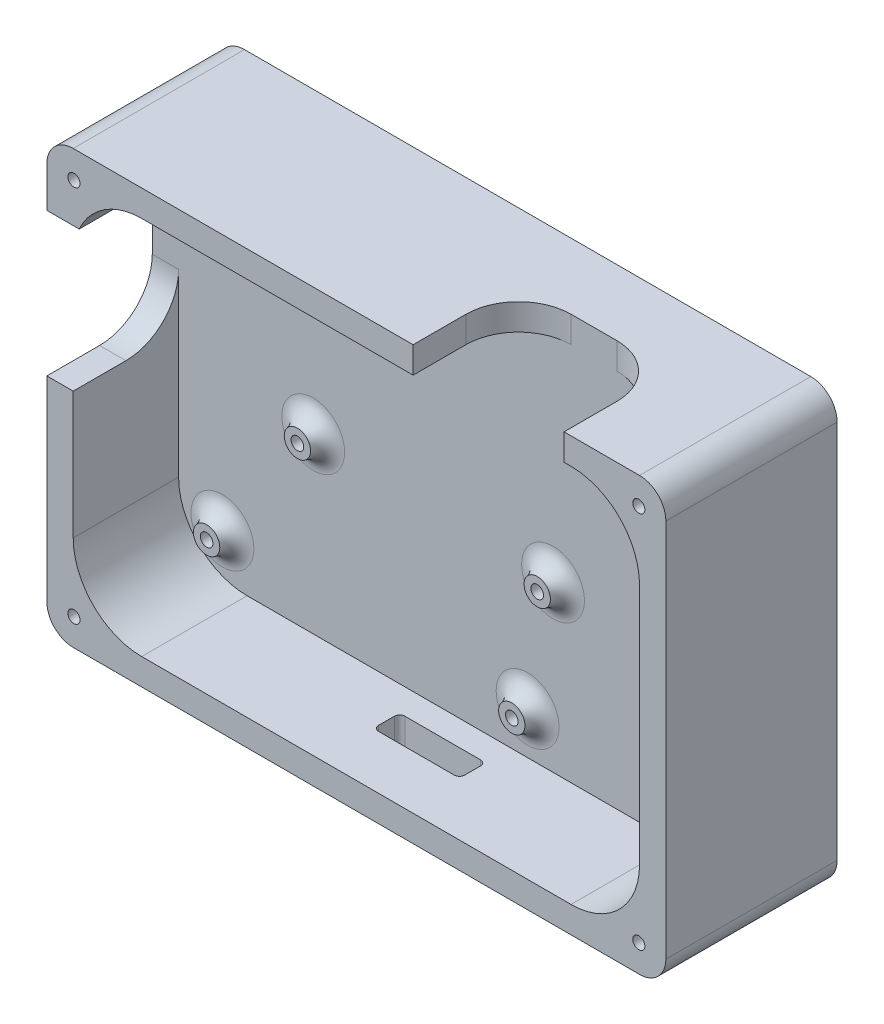
SolidWorks part; units mm, degrees
ref_plane "Front Plane" through (0, 0, 0) normal (0, 0, 1) x (1, 0, 0)
ref_plane "Top Plane" through (0, 0, 0) normal (0, 1, 0) x (1, 0, 0)
ref_plane "Right Plane" through (0, 0, 0) normal (1, 0, 0) x (0, 0, -1)
ref_plane "Plane1" through (0, 0, 1267.0007) normal (0, 0, -1) x (-1, 0, 0)
sketch "Sketch1" plane through (0, 0, 1267.0007) normal (0, 0, -1) x (-1, 0, 0)
  line L0 (-695.5296, 837.4474) -> (-695.5296, 897.8994) construction
  line L1 (-700.5296, 903.6614) -> (-593.0698, 903.6614)
  line L2 (-700.5296, 903.6614) -> (-700.5296, 831.66)
  line L3 (-700.5296, 831.66) -> (-593.0698, 831.66)
  line L4 (-593.0698, 903.6614) -> (-593.0698, 831.66)
  line L5 (-694.7676, 898.6614) -> (-598.8318, 898.6614) construction
  line L6 (-598.0698, 897.8994) -> (-598.0698, 837.4474) construction
  dimension "D1" = 5
  dimension "D2" = 5
  dimension "D3" = 5
  dimension "D4" = 5
extrude "Boss-Extrude1" add sketch "Sketch1" along normal blind 5
sketch "Sketch2" plane through (0, 0, 1267.0007) normal (0, 0, 1) x (1, 0, 0)
  circle A0 centre (692.0598, 895.8747) radius 2.5
  circle A1 centre (601.3798, 839.9968) radius 2.5
  circle A2 centre (692.0598, 862.8547) radius 2.5
  circle A3 centre (664.1198, 862.8547) radius 2.5
  circle A4 centre (602.0195, 895.2324) radius 2.5
  circle A5 centre (618.6145, 864.4774) radius 2.5
  circle A6 centre (659.2965, 839.6699) radius 2.5
  dimension "D1" = 5
extrude "Boss-Extrude2" add sketch "Sketch2" along normal up to surface (3 mm away)
fillet "Fillet1" radius 3.5 7 edges at (689.5598, 895.8747, 1267.0007) (689.5598, 862.8547, 1267.0007) (661.6198, 862.8547, 1267.0007) (616.1145, 864.4774, 1267.0007) (656.7965, 839.6699, 1267.0007) (599.5195, 895.2324, 1267.0007) (598.8798, 839.9968, 1267.0007)
sketch "Sketch3" plane through (0, 0, 1267.0007) normal (0, 0, 1) x (1, 0, 0)
  line L0 (700.5296, 903.6614) -> (700.5296, 831.66) construction
  line L1 (694.5296, 837.66) -> (684.5296, 837.66)
  line L2 (694.5296, 837.66) -> (694.5296, 855.66)
  line L3 (694.5296, 855.66) -> (684.5296, 855.66)
  line L4 (684.5296, 837.66) -> (684.5296, 855.66)
  line L5 (700.5296, 831.66) -> (593.0698, 831.66) construction
  point P8 (697.5296, 852.6101)
  dimension "D1" = 6
  dimension "D2" = 6
  dimension "D3" = 10
  dimension "D4" = 18
extrude "Cut-Extrude1" cut sketch "Sketch3" against normal through all
sketch "Sketch4" plane through (0, 0, 1262.0007) normal (0, 0, -1) x (-1, 0, 0)
  line L0 (-593.0698, 903.6614) -> (-700.5296, 903.6614) construction
  line L1 (-700.5296, 903.6614) -> (-593.0698, 903.6614)
  line L2 (-700.5296, 903.6614) -> (-700.5296, 831.66)
  line L3 (-700.5296, 831.66) -> (-593.0698, 831.66)
  line L4 (-593.0698, 903.6614) -> (-593.0698, 831.66)
  line L5 (-705.5296, 908.6614) -> (-588.0698, 908.6614)
  line L6 (-705.5296, 908.6614) -> (-705.5296, 826.66)
  line L7 (-705.5296, 826.66) -> (-588.0698, 826.66)
  line L8 (-588.0698, 908.6614) -> (-588.0698, 826.66)
  dimension "D1" = 5
  dimension "D2" = 5
  dimension "D3" = 5
  dimension "D4" = 5
extrude "Boss-Extrude3" add sketch "Sketch4" against normal blind 25
fillet "Fillet2" radius 13 4 edges at (700.5296, 903.6614, 1277.0007) (593.0698, 903.6614, 1277.0007) (593.0698, 831.66, 1277.0007) (700.5296, 831.66, 1277.0007)
fillet "Fillet4" radius 5 4 edges at (588.0698, 826.66, 1274.5007) (705.5296, 826.66, 1274.5007) (588.0698, 908.6614, 1274.5007) (705.5296, 908.6614, 1274.5007)
sketch "Sketch5" plane through (588.0698, 0, 0) normal (-1, 0, 0) x (0, 0, 1)
  line L0 (1262.0007, 831.66) -> (1262.0007, 903.6614) construction
  line L1 (1267.0007, 895.9849) -> (1287.0007, 895.9849)
  line L2 (1267.0007, 895.9849) -> (1267.0007, 868.7849)
  line L3 (1267.0007, 868.7849) -> (1287.0007, 868.7849)
  line L4 (1287.0007, 895.9849) -> (1287.0007, 868.7849)
  line L5 (1287.0007, 831.66) -> (1287.0007, 903.6614) construction
  dimension "D1" = 10
  dimension "D2" = 10
  dimension "D3" = 5
extrude "Cut-Extrude2" cut sketch "Sketch5" against normal up to next
sketch "Sketch6" plane through (0, 908.6614, 0) normal (0, 1, 0) x (1, 0, 0)
  line L0 (593.0698, -1287.0007) -> (700.5296, -1287.0007) construction
  line L1 (686.2098, -1287.0007) -> (657.5698, -1287.0007)
  line L2 (686.2098, -1287.0007) -> (686.2098, -1267.0007)
  line L3 (686.2098, -1267.0007) -> (657.5698, -1267.0007)
  line L4 (657.5698, -1287.0007) -> (657.5698, -1267.0007)
  line L5 (593.0698, -1262.0007) -> (700.5296, -1262.0007) construction
  dimension "D1" = 10
  dimension "D2" = 10
  dimension "D3" = 5
extrude "Cut-Extrude3" cut sketch "Sketch6" against normal up to next
sketch "Sketch7" plane through (0, 826.66, 0) normal (0, -1, 0) x (1, 0, 0)
  line L0 (651.9672, 1271.8248) -> (648.9707, 1271.8248) construction
  line L1 (639.8389, 1276.8248) -> (656.1839, 1276.8248)
  line L2 (639.8389, 1276.8248) -> (639.8389, 1271.8248)
  line L3 (639.8389, 1271.8248) -> (656.1839, 1271.8248)
  line L4 (656.1839, 1276.8248) -> (656.1839, 1271.8248)
  line L5 (633.3239, 1276.8248) -> (656.1839, 1276.8248) construction
extrude "Cut-Extrude4" cut sketch "Sketch7" against normal up to next
fillet "Fillet6" radius 10 4 edges at (591.1398, 895.9849, 1267.0007) (590.5698, 868.7849, 1267.0007) (657.5698, 906.1614, 1267.0007) (686.2098, 906.1614, 1267.0007)
sketch "Sketch8" plane through (0, 0, 1262.0007) normal (0, 0, -1) x (-1, 0, 0)
  line L0 (-680.5296, 888.66) -> (-694.5296, 855.66)
  line L1 (-680.5296, 888.66) -> (-615.5296, 888.66)
  line L2 (-680.5296, 888.66) -> (-680.5296, 846.66) construction
  line L3 (-680.5296, 846.66) -> (-615.5296, 846.66)
  line L4 (-615.5296, 888.66) -> (-615.5296, 846.66)
  line L5 (-694.5296, 855.66) -> (-694.5296, 837.66)
  line L6 (-694.5296, 837.66) -> (-684.5296, 837.66)
  line L7 (-684.5296, 837.66) -> (-680.5296, 846.66)
  line L8 (-700.5296, 826.66) -> (-593.0698, 826.66) construction
  line L9 (-705.5296, 903.6614) -> (-705.5296, 831.66) construction
  line L10 (-705.5296, 903.6614) -> (-705.5296, 831.66)
  line L11 (-700.5296, 826.66) -> (-593.0698, 826.66)
  line L12 (-588.0698, 831.66) -> (-588.0698, 903.6614)
  line L13 (-700.5296, 908.6614) -> (-593.0698, 908.6614)
  arc A0 (-700.5296, 908.6614) -> (-705.5296, 903.6614) centre (-700.5296, 903.6614) ccw
  arc A1 (-593.0698, 908.6614) -> (-588.0698, 903.6614) centre (-593.0698, 903.6614) cw
  arc A2 (-588.0698, 831.66) -> (-593.0698, 826.66) centre (-593.0698, 831.66) cw
  arc A3 (-705.5296, 831.66) -> (-700.5296, 826.66) centre (-700.5296, 831.66) ccw
  dimension "D1" = 42
  dimension "D2" = 65
  dimension "D3" = 20
  dimension "D4" = 25
extrude "Boss-Extrude4" add sketch "Sketch8" along normal blind 7.5
sketch "Sketch9" plane through (0, 0, 1287.0007) normal (0, 0, 1) x (1, 0, 0)
  line L0 (589.5342, 907.1969) -> (596.8774, 899.8538) construction
  line L1 (588.0698, 895.9849) -> (588.0698, 903.6614) construction
  line L2 (705.5296, 867.6607) -> (719.7043, 867.6607) construction
  line L3 (705.5296, 903.6614) -> (705.5296, 831.66) construction
  line L4 (646.7997, 826.66) -> (646.7997, 819.6754) construction
  line L5 (700.5296, 826.66) -> (593.0698, 826.66) construction
  arc A0 (593.0698, 908.6614) -> (588.0698, 903.6614) centre (593.0698, 903.6614) ccw construction
  arc A1 (606.0698, 903.6614) -> (594.2097, 895.9849) centre (606.0698, 890.6614) ccw construction
  point P18 (593.2058, 903.5254)
  point P19 (700.3935, 903.5254)
  point P20 (593.2058, 831.796)
  point P21 (700.3935, 831.796)
  dimension "D1" = 45
hole_wizard "M2.5 Clearance Hole1" positions "Sketch9" profile "Sketch11" hole size "M2.5" standard "ANSI Metric"
sketch "Sketch11" plane through (700.3935, 831.796, 1287.0007) normal (1, 0, 0) x (0, -1, 0)
  line L0 (0, 0) -> (0, 8.691)
  line L1 (0, 8.691) -> (1.15, 8)
  line L2 (1.15, 8) -> (1.15, 0)
  line L5 (1.15, 0) -> (0, 0)
  line L10 (0, 8.691) -> (-1.15, 8) construction
  line L11 (0, -6.35) -> (0, 107.95) construction
  dimension "Hole Dia." = 2.3
  dimension "Hole Depth" = 8
  dimension "Drill Angle" = 118
ref_plane "Plane2" through (0, 0, 1270.7507) normal (0, 0, 1) x (1, 0, 0)
mirror "Mirror1" about plane through (0, 0, 1270.7507) normal (0, 0, 1) of "M2.5 Clearance Hole1"
fillet "Fillet7" radius 10 1 edges at (680.5296, 846.66, 1258.2507)
fillet "Fillet9" radius 3 3 edges at (680.5296, 888.66, 1258.2507) (615.5296, 888.66, 1258.2507) (615.5296, 846.66, 1258.2507)
fillet "Fillet10" radius 1 4 edges at (656.1839, 829.16, 1276.8248) (656.1839, 829.16, 1271.8248) (639.8389, 829.16, 1271.8248) (639.8389, 829.16, 1276.8248)
sketch "Sketch12" plane through (0, 0, 1270.0007) normal (0, 0, 1) x (1, 0, 0)
  point P0 (601.3798, 839.9968)
  point P1 (659.2965, 839.6699)
  point P3 (692.0498, 862.8347)
  point P5 (664.1098, 862.8347)
  point P7 (692.0598, 895.8747)
  point P9 (618.6145, 864.4774)
hole_wizard "M2.5 Clearance Hole2" positions "Sketch12" profile "Sketch13" hole size "M2.5" standard "ANSI Metric"
sketch "Sketch13" plane through (601.3798, 839.9968, 1270.0007) normal (1, 0, 0) x (0, -1, 0)
  line L0 (0, 0) -> (0, 7.721)
  line L1 (0, 7.721) -> (1.2, 7)
  line L2 (1.2, 7) -> (1.2, 0)
  line L5 (1.2, 0) -> (0, 0)
  line L10 (0, 7.721) -> (-1.2, 7) construction
  line L11 (0, -6.35) -> (0, 107.95) construction
  dimension "Hole Dia." = 2.4
  dimension "Hole Depth" = 7
  dimension "Drill Angle" = 118
